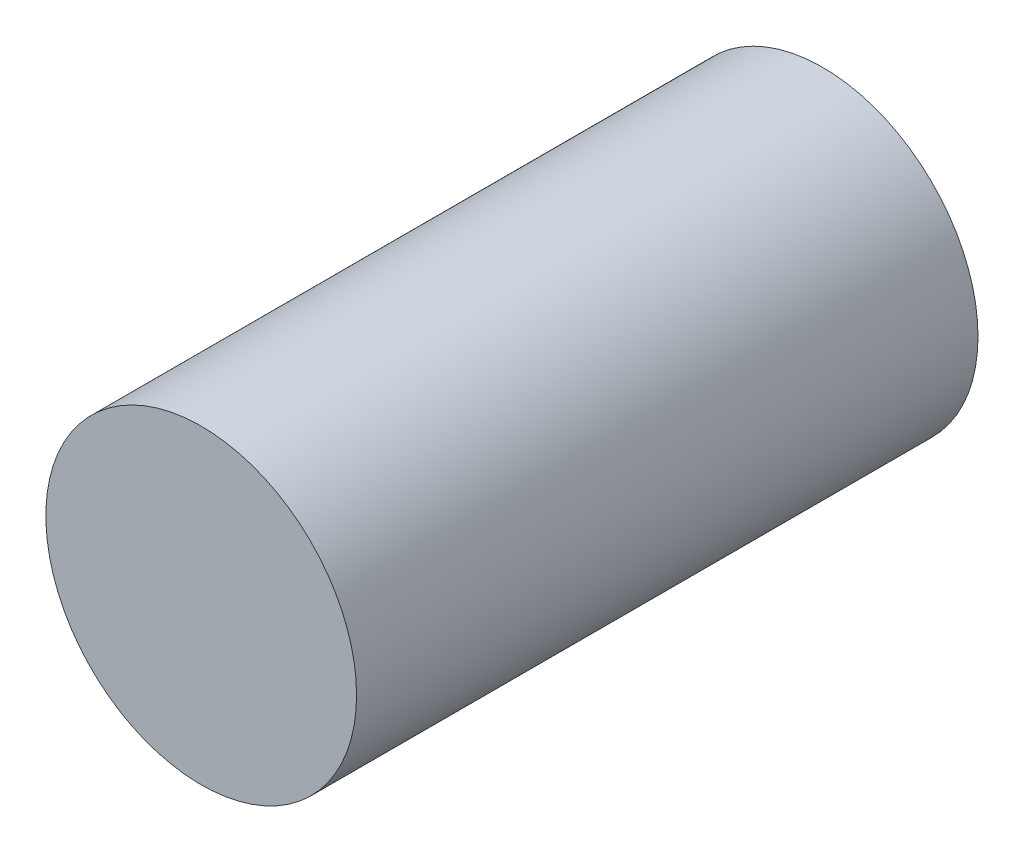
SolidWorks part; units mm, degrees
ref_plane "Front Plane" through (0, 0, 0) normal (0, 0, 1) x (1, 0, 0)
ref_plane "Top Plane" through (0, 0, 0) normal (0, 1, 0) x (1, 0, 0)
ref_plane "Right Plane" through (0, 0, 0) normal (1, 0, 0) x (0, 0, -1)
sketch "Sketch1" plane through (0, 0, 0) normal (0, 1, 0) x (1, 0, 0)
  line L0 (2.1, -5.5) -> (1.6, -5.5)
  line L1 (0, 0) -> (2.1, 0)
  line L2 (0, 0) -> (0, -21)
  line L3 (1, -20) -> (1.6, -20)
  line L4 (2.1, 0) -> (2.1, -5.5)
  line L5 (1.6, -5.5) -> (1.6, -7.5)
  line L6 (1.6, -7.5) -> (2.1, -7.5)
  line L7 (2.1, -7.5) -> (2.1, -19.5)
  arc A0 (0, -21) -> (1, -20) centre (0, -20) ccw
  arc A1 (1.6, -20) -> (2.1, -19.5) centre (1.6, -19.5) ccw
  dimension "D6" = 1
  dimension "D7" = 0.5
  dimension "D1" = 2.1
  dimension "D2" = 20
  dimension "D3" = 0.5
  dimension "D4" = 2
  dimension "D5" = 12.5
revolve "Revolve1" add sketch "Sketch1" angle 360 about L2
fillet "Fillet1" radius 0.5 2 edges at (-2.1, 0, 7.5) (-2.1, 0, 5.5)
sketch "Sketch2" plane through (0, 0, 0) normal (1, 0, 0) x (0, 0, -1)
  line L0 (-18.433, 0.25) -> (-15.183, 5.8792)
  line L1 (-15.183, 5.8792) -> (-14.75, 5.6292)
  line L2 (-14.75, 5.6292) -> (-18, 0)
  line L3 (-18, 0) -> (-18.433, 0.25)
  line L4 (0, 0) -> (-21, 0) construction
  dimension "D1" = 60
  dimension "D2" = 6.5
  dimension "D3" = 0.5
  dimension "D4" = 2
revolve "Revolve2" add sketch "Sketch2" angle 360 about L2
fillet "Fillet2" radius 0.3 1 edges at (0, 5.8792, 15.183)
pattern_circular "CirPattern1" count 4 over 360 about axis through (0, 0, 0) along (0, 0, 1) of "Revolve2", "Fillet2"
sketch "Sketch3" plane through (0, 0, 0) normal (0, 0, 1) x (1, 0, 0)
  circle A0 centre (0, 0) radius 10
  dimension "D1" = 20
extrude "Boss-Extrude1" add sketch "Sketch3" along normal blind 40 separate body
combine bodies "Combine1" operation type subtract main body 104 bodies to subtract 103
